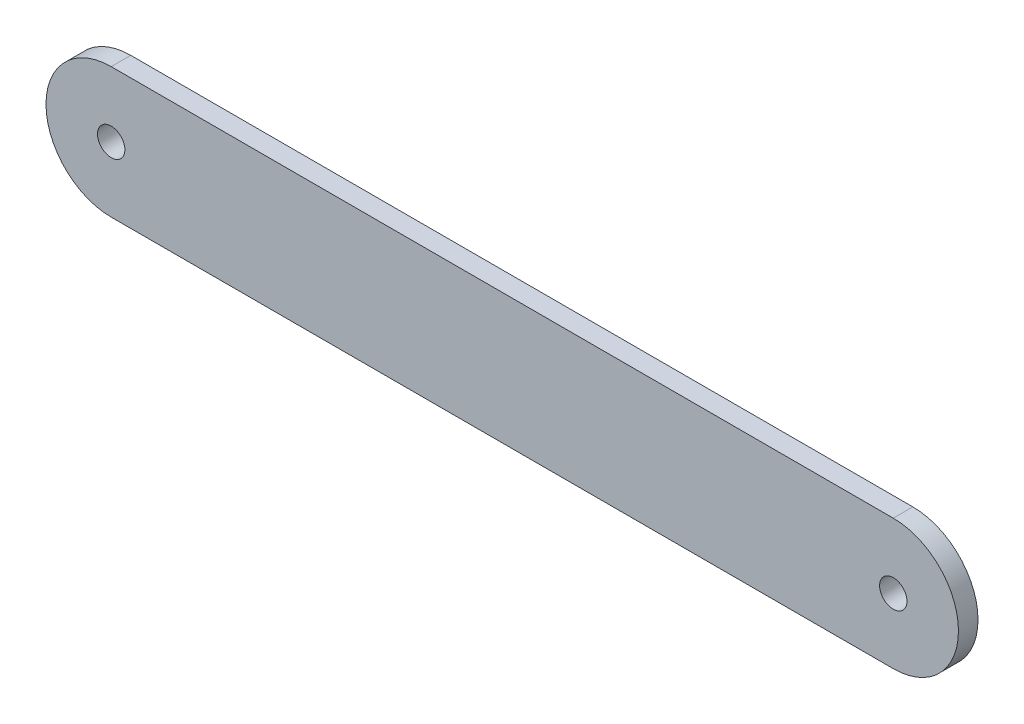
SolidWorks part; units mm, degrees
ref_plane "Front Plane" through (0, 0, 0) normal (0, 0, 1) x (1, 0, 0)
ref_plane "Top Plane" through (0, 0, 0) normal (0, 1, 0) x (1, 0, 0)
ref_plane "Right Plane" through (0, 0, 0) normal (1, 0, 0) x (0, 0, -1)
sketch "Sketch1" plane through (0, 0, 0) normal (0, 0, 1) x (1, 0, 0)
  line L0 (-60, 0) -> (60, 0) construction
  line L1 (-60, 10) -> (60, 10)
  line L2 (-60, -10) -> (60, -10)
  line L3 (0, 10) -> (0, -10) construction
  arc A0 (-60, 10) -> (-60, -10) centre (-60, 0) ccw
  arc A1 (60, -10) -> (60, 10) centre (60, 0) ccw
  circle A2 centre (-60, 0) radius 2.1
  circle A3 centre (60, 0) radius 2.1
  point P2 (0, 0)
  dimension "D2" = 10
  dimension "D3" = 4.2
  dimension "D1" = 120
extrude "Boss-Extrude1" add sketch "Sketch1" along normal blind 3
equation "\"L1\"= 120mm'Upper arm"
equation "\"L3\"= 75mm'Wrist→TCP"
equation "\"h0\"= 75mm'Shoulder height"
equation "\"t_link\"= 3mm'Link plate thickness"
equation "\"t_bracket\"= 4mm'Bracket thickness"
equation "\"d_pin\"= 4mm'Pin diameter (M4)"
equation "\"c_fit\"= 0.2mm'Nominal clearance - measured PLA 2026-10-01"
equation "\"L2\"= 120mm'Forearm"
equation "\"c_fit_pivot\"= \"c_fit\" + 0.05mm'Gripper pivot clearance - chosen 0.25 mm 2026-10-01"
equation "\"d_pin_gripper\"= 3mm'Gripper pivot diameter"
equation "\"w_link\"= 20mm'Link plate depth (bending direction)"
equation "\"w_gap\"= 20mm'Twin-plate gap - provisional, set by elbow servo mount"
equation "\"D1@Sketch1\"=\"L1\""
equation "\"D2@Sketch1\"=\"w_link\"/2"
equation "\"D3@Sketch1\"=\"d_pin\"+\"c_fit\""
equation "\"D1@Boss-Extrude1\"=\"t_link\""
